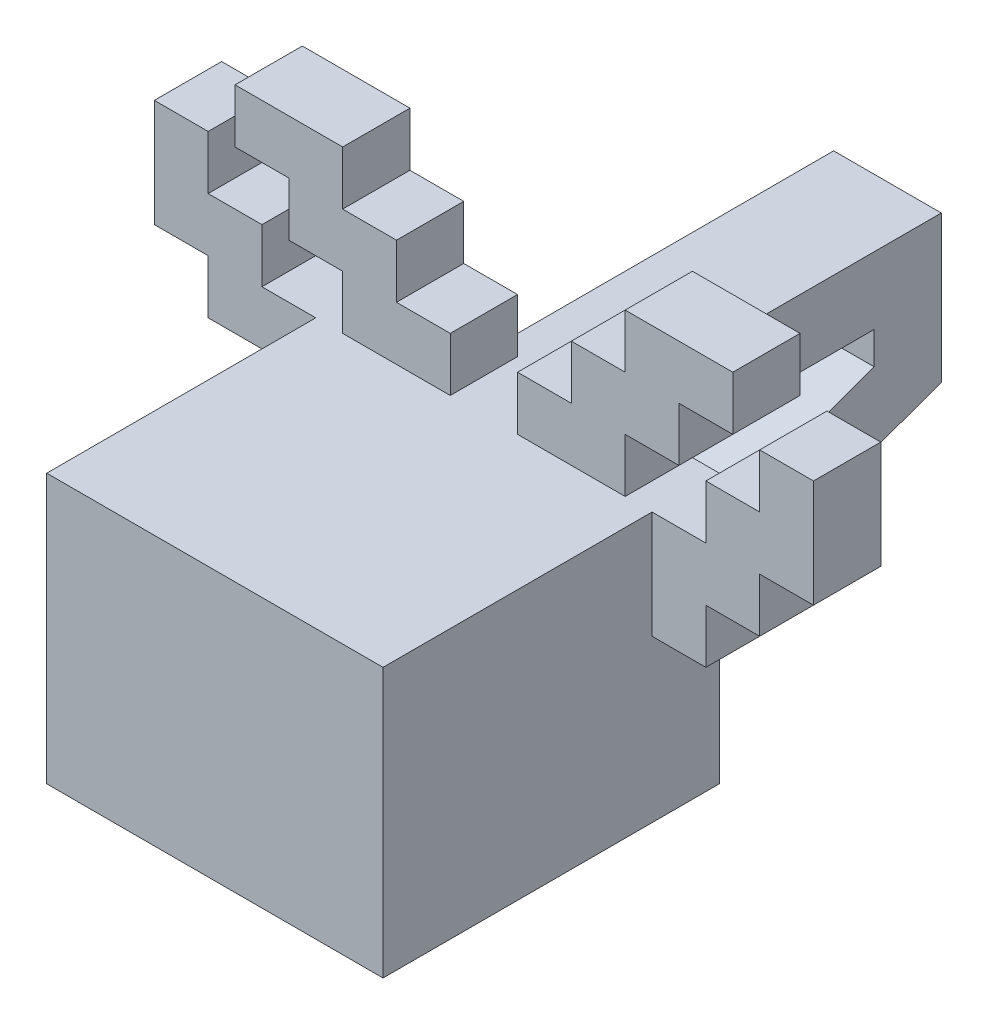
SolidWorks part; units mm, degrees
ref_plane "Спереди" through (0, 0, 0) normal (0, 0, 1) x (1, 0, 0)
ref_plane "Сверху" through (0, 0, 0) normal (0, 1, 0) x (1, 0, 0)
ref_plane "Справа" through (0, 0, 0) normal (1, 0, 0) x (0, 0, -1)
sketch "Эскиз1" plane through (0, 0, 0) normal (1, 0, 0) x (0, 0, -1)
  line L0 (0, 0) -> (0, 20)
  line L1 (0, 20) -> (50, 20)
  line L2 (50, 20) -> (50, 9.0993)
  line L3 (50, 9.0993) -> (25, 0)
  line L4 (25, 0) -> (0, 0)
  line L5 (30, 7.1407) -> (30, 15)
  line L6 (30, 15) -> (45, 15)
  line L7 (45, 15) -> (45, 12.6003)
  line L8 (45, 12.6003) -> (30, 7.1407)
  line L9 (25, 20) -> (25, 0)
  point P14 (16.9754, 20.396)
  dimension "D1" = 20
  dimension "D2" = 25
  dimension "D3" = 5
  dimension "D4" = 25
  dimension "D5" = 15
  dimension "D6" = 5
  dimension "D7" = 160
  dimension "D8" = 5
  dimension "D9" = 5
  dimension "D10" = 25
extrude "Бобышка-Вытянуть2" add sketch "Эскиз1" along normal mid plane 25 contours L9 L1 L0 L4 region at (0, 10, -12.5)
extrude "Бобышка-Вытянуть3" add sketch "Эскиз1<4>" along normal mid plane 8 contours L1 L9 L3 L2 L7 L8 L5 L6 region at (0, 10, -25.3202)
sketch "Эскиз1<4>" plane through (0, 0, 0) normal (1, 0, 0) x (0, 0, -1) same geometry as "Эскиз1"
sketch "Эскиз3" plane through (0, 0, -25) normal (0, 0, -1) x (-1, 0, 0)
  line L0 (-12.5, 12) -> (-16.5, 12)
  line L1 (-12.5, 20) -> (-12.5, 0) construction
  line L2 (-16.5, 12) -> (-16.5, 16)
  line L3 (-16.5, 16) -> (-20.5, 16)
  line L4 (-20.5, 16) -> (-20.5, 20)
  line L5 (-20.5, 20) -> (-24.5, 20)
  line L6 (-24.5, 20) -> (-24.5, 28)
  line L7 (-24.5, 28) -> (-20.5, 28)
  line L8 (-20.5, 28) -> (-20.5, 24)
  line L9 (-20.5, 24) -> (-16.5, 24)
  line L10 (-16.5, 24) -> (-16.5, 20)
  line L11 (-16.5, 20) -> (-12.5, 20)
  line L12 (-12.5, 20) -> (-12.5, 12)
  line L13 (0, 36.6239) -> (0, -3.5792) construction
  line L14 (20.5, 20) -> (24.5, 20)
  line L15 (20.5, 16) -> (20.5, 20)
  line L16 (16.5, 16) -> (20.5, 16)
  line L17 (16.5, 12) -> (16.5, 16)
  line L18 (12.5, 12) -> (16.5, 12)
  line L19 (12.5, 20) -> (12.5, 12)
  line L20 (16.5, 20) -> (12.5, 20)
  line L21 (16.5, 24) -> (16.5, 20)
  line L22 (20.5, 24) -> (16.5, 24)
  line L23 (20.5, 28) -> (20.5, 24)
  line L24 (24.5, 28) -> (20.5, 28)
  line L25 (24.5, 20) -> (24.5, 28)
  line L26 (-10.5, 20) -> (-10.5, 24)
  line L27 (-12.5, 20) -> (-4, 20) construction
  line L28 (-10.5, 24) -> (-14.5, 24)
  line L29 (-14.5, 24) -> (-14.5, 28)
  line L30 (-14.5, 28) -> (-18.5, 28)
  line L31 (-18.5, 28) -> (-18.5, 32)
  line L32 (-18.5, 32) -> (-10.5, 32)
  line L33 (-10.5, 32) -> (-10.5, 28)
  line L34 (-10.5, 28) -> (-6.5, 28)
  line L35 (-6.5, 28) -> (-6.5, 24)
  line L36 (-6.5, 24) -> (-2.5, 24)
  line L37 (-2.5, 24) -> (-2.5, 20)
  line L38 (-4, 20) -> (4, 20) construction
  line L39 (-2.5, 20) -> (-10.5, 20)
  line L40 (10.5, 20) -> (10.5, 24)
  line L41 (10.5, 24) -> (14.5, 24)
  line L42 (14.5, 24) -> (14.5, 28)
  line L43 (14.5, 28) -> (18.5, 28)
  line L44 (18.5, 28) -> (18.5, 32)
  line L45 (18.5, 32) -> (10.5, 32)
  line L46 (10.5, 32) -> (10.5, 28)
  line L47 (10.5, 28) -> (6.5, 28)
  line L48 (6.5, 28) -> (6.5, 24)
  line L49 (6.5, 24) -> (2.5, 24)
  line L50 (2.5, 24) -> (2.5, 20)
  line L51 (2.5, 20) -> (10.5, 20)
  dimension "D1" = 4
  dimension "D2" = 8
  dimension "D3" = 4
  dimension "D4" = 4
  dimension "D5" = 8
  dimension "D6" = 4
  dimension "D7" = 4
  dimension "D8" = 4
  dimension "D9" = 4
  dimension "D10" = 4
  dimension "D11" = 4
  dimension "D12" = 4
  dimension "D13" = 4
  dimension "D14" = 4
  dimension "D15" = 4
  dimension "D16" = 4
  dimension "D17" = 8
  dimension "D18" = 4
  dimension "D19" = 8
  dimension "D20" = 2
  dimension "D21" = 4
  dimension "D22" = 4
extrude "Бобышка-Вытянуть4" add sketch "Эскиз3" against normal blind 5
